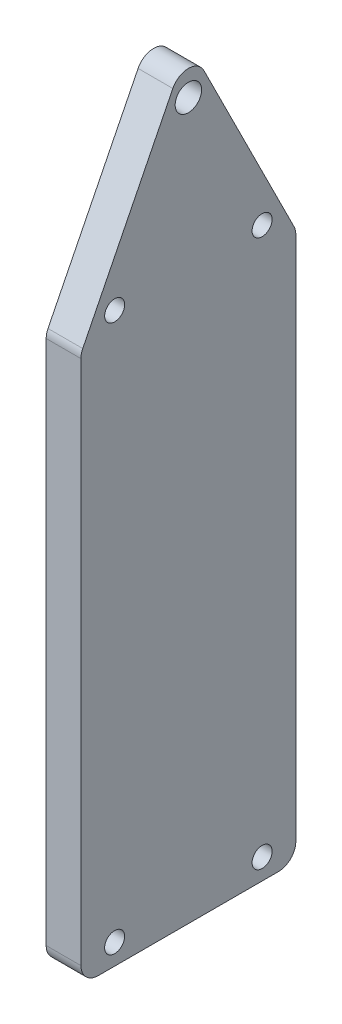
SolidWorks part; units mm, degrees
ref_plane "Front Plane" through (0, 0, 0) normal (0, 0, 1) x (1, 0, 0)
ref_plane "Top Plane" through (0, 0, 0) normal (0, 1, 0) x (1, 0, 0)
ref_plane "Right Plane" through (0, 0, 0) normal (1, 0, 0) x (0, 0, -1)
sketch "Sketch1" plane through (0, 0, 0) normal (1, 0, 0) x (0, 0, -1)
  line L0 (-13.4747, 0) -> (13.4747, 0) construction
  line L1 (0, 0) -> (0, 26.9494) construction
  line L2 (-13.4747, 0) -> (0, 26.9494) construction
  line L3 (0, 26.9494) -> (13.4747, 0) construction
  line L4 (13.4747, 0) -> (-13.4747, 0) construction
  line L5 (19.6394, -3.81) -> (-19.6394, -3.81)
  line L6 (-19.6394, -3.81) -> (0, 35.4688)
  line L7 (0, 35.4688) -> (19.6394, -3.81)
  line L8 (-13.4747, 0) -> (13.4747, 0) construction
  line L9 (-13.4747, 0) -> (-13.4747, -100) construction
  line L10 (13.4747, 0) -> (13.4747, -100) construction
  line L11 (-13.4747, -100) -> (13.4747, -100) construction
  line L12 (-19.6394, -3.81) -> (19.6394, -3.81)
  line L13 (-19.6394, -3.81) -> (-19.6394, -103.81)
  line L14 (19.6394, -3.81) -> (19.6394, -103.81)
  line L15 (-19.6394, -103.81) -> (19.6394, -103.81)
  circle A0 centre (-13.4747, 0) radius 1.8288
  circle A1 centre (0, 26.9494) radius 2.413
  circle A2 centre (13.4747, 0) radius 1.8288
  circle A3 centre (-13.4747, -100) radius 1.8288
  circle A4 centre (13.4747, -100) radius 1.8288
  point P4 (0, 0)
  dimension "D3" = 3.6576
  dimension "D4" = 4.826
  dimension "D1" = 26.9494
  dimension "D5" = 100
  dimension "D6" = 3.81
  dimension "D2" = 3.81
extrude "Boss-Extrude1" add sketch "Sketch1" along normal blind 6.35 contours L13 L15 L14 L5 A4 A3 | L7 L6 L5 A2 A1 A0 region at (0, -53.5616, 0) region at (0, 9.108, 0)
fillet "Fillet1" radius 3.175 5 edges at (3.175, 35.4688, 0) (3.175, -103.81, 19.6394) (3.175, -103.81, -19.6394) (3.175, -3.81, 19.6394) (3.175, -3.81, -19.6394)
